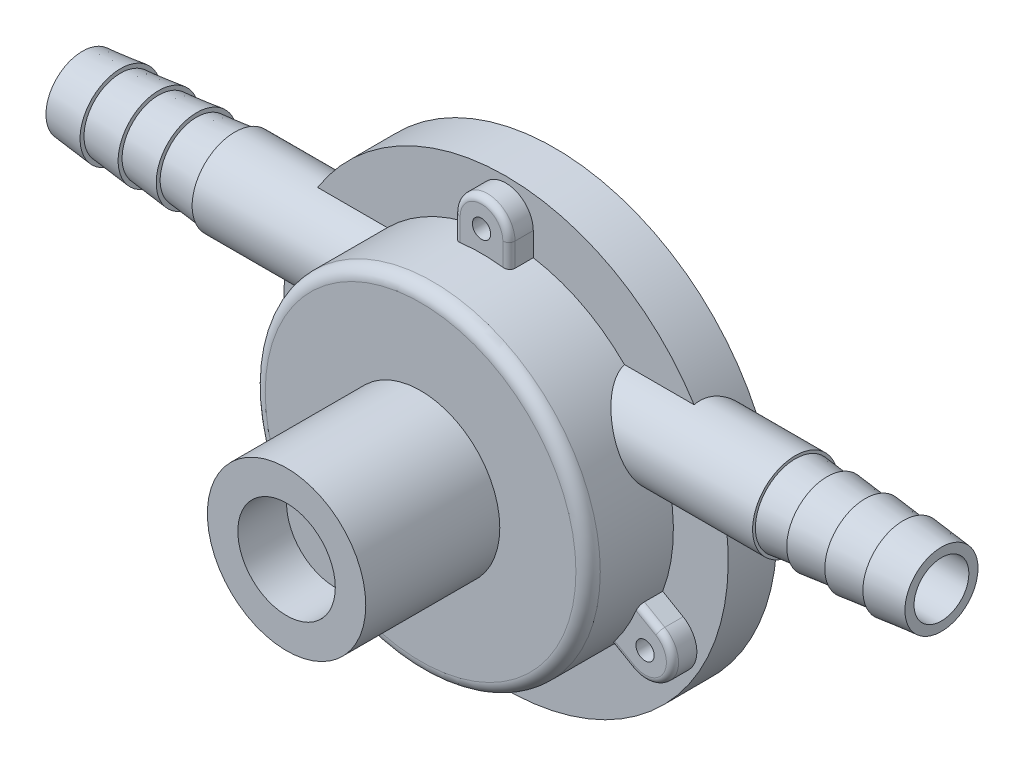
SolidWorks part; units mm, degrees
ref_plane "Front Plane" through (0, 0, 0) normal (0, 0, 1) x (1, 0, 0)
ref_plane "Top Plane" through (0, 0, 0) normal (0, 1, 0) x (1, 0, 0)
ref_plane "Right Plane" through (0, 0, 0) normal (1, 0, 0) x (0, 0, -1)
sketch "Sketch1" plane through (0, 0, 0) normal (0, 0, 1) x (1, 0, 0)
  circle A0 centre (0, 0) radius 36.5
  dimension "D1" = 73
extrude "Boss-Extrude1" add sketch "Sketch1" along normal blind 8
sketch "Sketch2" plane through (0, 0, 8) normal (0, 0, 1) x (1, 0, 0)
  circle A0 centre (0, 0) radius 27.5
  dimension "D1" = 55
extrude "Boss-Extrude2" add sketch "Sketch2" along normal blind 14
sketch "Sketch3" plane through (0, 0, 22) normal (0, 0, 1) x (1, 0, 0)
  circle A0 centre (0, 0) radius 13
  dimension "D1" = 26
extrude "Boss-Extrude3" add sketch "Sketch3" along normal blind 22
sketch "Sketch4" plane through (0, 0, 44) normal (0, 0, 1) x (1, 0, 0)
  circle A0 centre (0, 0) radius 8
  dimension "D1" = 16
extrude "Cut-Extrude1" cut sketch "Sketch4" against normal blind 8
ref_plane "Plane2" through (36.5, 0, 0) normal (1, 0, 0) x (0, 0, -1)
sketch "Sketch6" plane through (36.5, 0, 0) normal (1, 0, 0) x (0, 0, -1)
  line L0 (0, -36.5) -> (0, 36.5) construction
  line L2 (-8, 27.5) -> (-22, 27.5) construction
  circle A0 centre (-7, 12.5) radius 7
  dimension "D1" = 14
  dimension "D2" = 7
  dimension "D3" = 15
extrude "Boss-Extrude4" add sketch "Sketch6" along normal blind 10 and the other way blind 82
sketch "Sketch8" plane through (0, 0, 0) normal (0, 0, -1) x (-1, 0, 0)
  circle A1 centre (0, 0) radius 8 construction
  arc A3 (-17.6535, 13.95) -> (17.6535, 13.95) centre (0, 0) ccw
  arc A4 (-17.6535, 13.95) -> (17.6535, 13.95) centre (0, -22.5) cw
  point P2 (0, -8)
  dimension "D1" = 45
  dimension "D2" = 40.5
extrude "Cut-Extrude2" cut sketch "Sketch8" against normal blind 12
sketch "Sketch10" plane through (46.5, 0, 0) normal (1, 0, 0) x (0, 0, -1)
  circle A0 centre (-7, 12.5) radius 4.5
  dimension "D1" = 9
sketch "Sketch11" plane through (0, 0, 0) normal (0, 0, -1) x (-1, 0, 0)
  circle A0 centre (0, 31) radius 1.5
  circle A1 centre (0, 0) radius 36.5 construction
  circle A7 centre (26.8468, -15.5) radius 1.5
  circle A8 centre (-26.8468, -15.5) radius 1.5
  arc A9 (34.2929, 12.5) -> (-34.2929, 12.5) centre (0, 0) ccw construction
  point P13 (0, -1)
  point P14 (0, 0)
  point P15 (0, -1)
  dimension "D1" = 3
  dimension "D3" = 3
  dimension "D4" = 26.8468
  dimension "D5" = 31
  dimension "D2" = 31
extrude "Cut-Extrude4" cut sketch "Sketch11" against normal through all
fillet "Fillet1" radius 2 1 edges at (27.5, 0, 22)
extrude "Cut-Extrude5" cut sketch "Sketch10" against normal through all
sketch "Sketch12" plane through (0, 0, 36) normal (0, 0, 1) x (1, 0, 0)
  circle A0 centre (0, 0) radius 3.2
  dimension "D1" = 6.4
extrude "Cut-Extrude6" cut sketch "Sketch12" against normal through all
sketch "Sketch13" plane through (0, 0, 0) normal (0, 0, -1) x (-1, 0, 0)
  circle A0 centre (0, 0) radius 25
  circle A1 centre (0, 0) radius 27.3
extrude "Cut-Extrude7" cut sketch "Sketch13" against normal blind 1.2
sketch "Sketch14" plane through (0, 0, 8) normal (0, 0, 1) x (1, 0, 0)
  line L0 (4.5, 31) -> (4.5, 27.1293)
  line L1 (-4.5, 31) -> (-4.5, 27.1293)
  line L2 (29.0968, -11.6029) -> (25.7447, -9.6675)
  line L3 (24.5968, -19.3971) -> (21.2447, -17.4618)
  line L4 (-24.5968, -19.3971) -> (-21.2447, -17.4618)
  line L5 (-29.0968, -11.6029) -> (-25.7447, -9.6675)
  arc A2 (4.5, 31) -> (-4.5, 31) centre (0, 31) ccw
  arc A3 (19.4627, 19.4282) -> (-19.4627, 19.4282) centre (0, 0) ccw construction
  arc A4 (24.5968, -19.3971) -> (29.0968, -11.6029) centre (26.8468, -15.5) ccw
  arc A5 (-29.0968, -11.6029) -> (-24.5968, -19.3971) centre (-26.8468, -15.5) ccw
  arc A6 (21.2447, -17.4618) -> (25.7447, -9.6675) centre (0, 0) ccw
  arc A7 (-25.7447, -9.6675) -> (-21.2447, -17.4618) centre (0, 0) ccw
  arc A8 (4.5, 27.1293) -> (-4.5, 27.1293) centre (0, 0) ccw
  point P27 (0, 0)
  dimension "D1" = 9
  dimension "D2" = 3
extrude "Boss-Extrude5" add sketch "Sketch14" along normal blind 4
fillet "Fillet2" radius 1 9 edges at (4.5, 29.0647, 12) (-4.5, 29.0647, 12) (22.9207, -18.4294, 12) (27.4207, -10.6352, 12) (-27.4207, -10.6352, 12) (-22.9207, -18.4294, 12) (0, 35.5, 12) (30.7439, -17.75, 12) (-30.7439, -17.75, 12)
sketch "Sketch15" plane through (0, 0, 0) normal (0, 0, -1) x (-1, 0, 0)
  circle A0 centre (0, 31) radius 1.5
  circle A1 centre (26.8468, -15.5) radius 1.5
  circle A2 centre (-26.8468, -15.5) radius 1.5
  point P10 (0, 0)
  dimension "D1" = 3
  dimension "D4" = 26.8468
  dimension "D3" = 15.5
  dimension "D2" = 3
extrude "Cut-Extrude8" cut sketch "Sketch15" against normal through all
ref_plane "Plane3" through (0, 12.5, 0) normal (0, 1, 0) x (1, 0, 0)
sketch "Sketch16" plane through (0, 12.5, 0) normal (0, 1, 0) x (1, 0, 0)
  line L0 (-70.5, -13) -> (-64.25, -13.65)
  line L3 (-45.5, 0) -> (-45.5, -14) construction
  line L4 (-70.5, -1) -> (-45.5, -1) construction
  line L5 (0, 0) -> (0, -60.1535) construction
  line L6 (70.5, -13) -> (70.5, -7)
  line L7 (-64.25, -13.65) -> (-64.25, -13)
  line L8 (-64.25, -13) -> (-58, -13.65)
  line L9 (-58, -13.65) -> (-58, -13)
  line L10 (-58, -13) -> (-51.75, -13.65)
  line L11 (-51.75, -13.65) -> (-51.75, -13)
  line L12 (-51.75, -13) -> (-45.5, -13.65)
  line L13 (-45.5, -13.65) -> (-45.5, -13)
  line L14 (70.5, -7) -> (45.5, -7)
  line L15 (-70.5, -7) -> (-45.5, -7)
  line L16 (-70.5, -13) -> (-70.5, -7)
  line L17 (-45.5, -7) -> (-45.5, -13)
  line L18 (45.5, -7) -> (45.5, -13)
  line L19 (45.5, -13.65) -> (45.5, -13)
  line L20 (51.75, -13) -> (45.5, -13.65)
  line L21 (51.75, -13.65) -> (51.75, -13)
  line L22 (58, -13) -> (51.75, -13.65)
  line L23 (58, -13.65) -> (58, -13)
  line L24 (64.25, -13) -> (58, -13.65)
  line L25 (64.25, -13.65) -> (64.25, -13)
  line L26 (70.5, -13) -> (64.25, -13.65)
  point P0 (-45.5, -7)
  line B0 (-70.5, -13) -> (-70.5, -1) construction
  line B1 (-70.5, -13) -> (-45.5, -13) construction
  line B2 (-45.5, -13) -> (-45.5, -1) construction
  line B3 (-70.5, -13) -> (-45.5, -1) construction
  line B4 (-45.5, -13) -> (-70.5, -1) construction
  line B5 (-68.289, -13.65) -> (-41.9667, -13.65) construction
  line B6 (-58, -7) -> (-26.614, -7) construction
  line B7 (-70.5, -12.2) -> (-45.5, -12.2)
sketch_block_instance "Block1-1"
sketch_block "Block1" parameters "D1"=12, "D2"=25, "D3"=0.65, "D4"=0.8
revolve "Revolve1" add sketch "Sketch16" angle 360 about L14 region at (-57.6991, 12.5, 12.7781) region at (-58, 12.5, 9.6)
sketch "Sketch17" plane through (70.5, 0, 0) normal (1, 0, 0) x (0, 0, -1)
  circle A0 centre (-7, 12.5) radius 4.5
  dimension "D1" = 9
extrude "Cut-Extrude9" cut sketch "Sketch17" against normal through all
